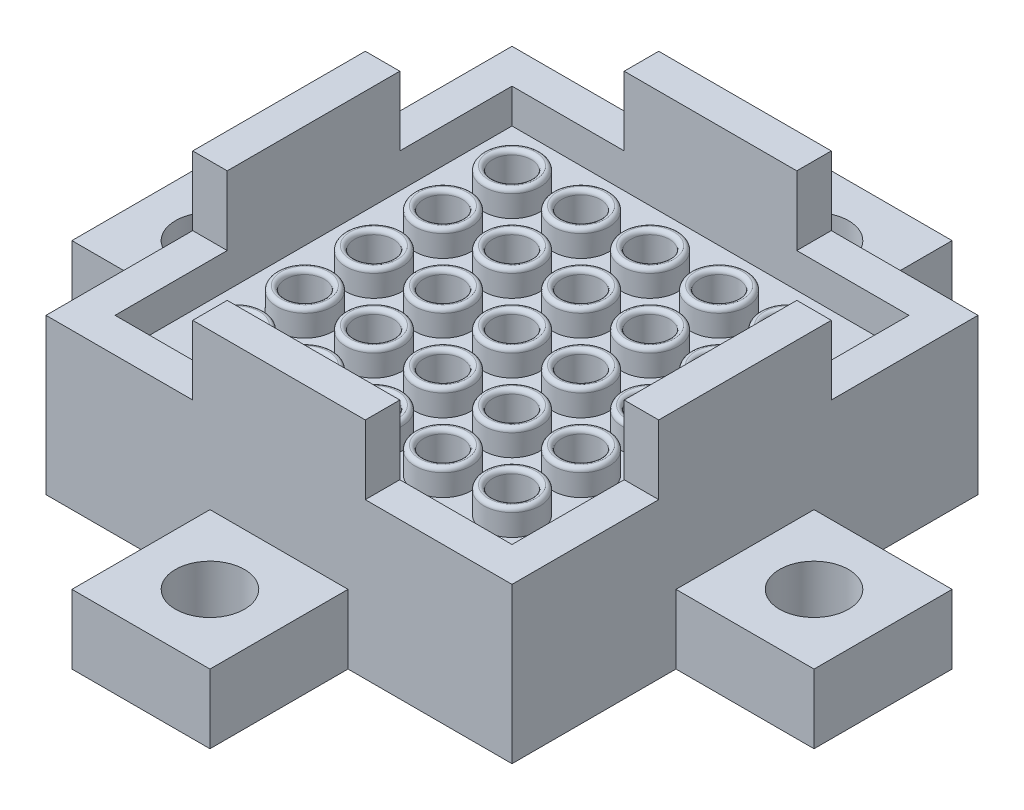
SolidWorks part; units mm, degrees
ref_plane "Front Plane" through (0, 0, 0) normal (0, 0, 1) x (1, 0, 0)
ref_plane "Top Plane" through (0, 0, 0) normal (0, 1, 0) x (1, 0, 0)
ref_plane "Right Plane" through (0, 0, 0) normal (1, 0, 0) x (0, 0, -1)
sketch "Sketch1" plane through (0, 0, 0) normal (0, 1, 0) x (1, 0, 0)
  line L0 (-13.5, 13.5) -> (13.5, 13.5)
  line L1 (-11.5, -11.5) -> (11.5, -11.5)
  line L2 (-11.5, -11.5) -> (-11.5, 11.5)
  line L3 (-11.5, 11.5) -> (11.5, 11.5)
  line L4 (11.5, -11.5) -> (11.5, 11.5)
  line L5 (-11.5, -11.5) -> (11.5, 11.5) construction
  line L6 (-11.5, 11.5) -> (11.5, -11.5) construction
  line L7 (13.5, -13.5) -> (13.5, 13.5)
  line L8 (-13.5, -13.5) -> (13.5, -13.5)
  line L9 (-13.5, -13.5) -> (-13.5, 13.5)
  point P0 (0, 0)
  dimension "D1" = 23
  dimension "D2" = 2
extrude "Boss-Extrude1" add sketch "Sketch1" along normal blind 2
sketch "Sketch2" plane through (0, 0, 0) normal (0, -1, 0) x (1, 0, 0)
  line L1 (-13.5, 13.5) -> (13.5, 13.5)
  line L2 (-13.5, 13.5) -> (-13.5, -13.5)
  line L3 (-13.5, -13.5) -> (13.5, -13.5)
  line L4 (13.5, 13.5) -> (13.5, -13.5)
  line L5 (-13.5, 13.5) -> (13.5, -13.5) construction
  line L6 (-13.5, -13.5) -> (13.5, 13.5) construction
  point P0 (0, 0)
extrude "Boss-Extrude2" add sketch "Sketch2" along normal blind 2
sketch "Sketch3" plane through (0, -2, 0) normal (0, -1, 0) x (1, 0, 0)
  line L0 (-11.5, 11.5) -> (11.5, 11.5)
  line L1 (-13.5, -13.5) -> (13.5, -13.5)
  line L2 (-13.5, -13.5) -> (-13.5, 13.5)
  line L3 (-13.5, 13.5) -> (13.5, 13.5)
  line L4 (13.5, -13.5) -> (13.5, 13.5)
  line L5 (-13.5, -13.5) -> (13.5, 13.5) construction
  line L6 (-13.5, 13.5) -> (13.5, -13.5) construction
  line L7 (11.5, -11.5) -> (11.5, 11.5)
  line L8 (-11.5, -11.5) -> (11.5, -11.5)
  line L9 (-11.5, -11.5) -> (-11.5, 11.5)
  point P0 (0, 0)
  dimension "D1" = 2
extrude "Boss-Extrude3" add sketch "Sketch3" along normal blind 3
sketch "Sketch6" plane through (0, 0, 0) normal (0, 1, 0) x (1, 0, 0)
  line L0 (11.5, -11.5) -> (11.5, 11.5) construction
  line L1 (11.5, 11.5) -> (-11.5, 11.5) construction
  circle A0 centre (8, 8) radius 1.625
  dimension "D2" = 3.25
  dimension "D1" = 3.5
  dimension "D3" = 3.5
extrude "Boss-Extrude5" add sketch "Sketch6" along normal blind 1.5
sketch "Sketch7" plane through (0, 1.5, 0) normal (0, 1, 0) x (1, 0, 0)
  circle A0 centre (8, 8) radius 1.125
  circle A1 centre (8, 8) radius 1.625 construction
  dimension "D1" = 0.5
extrude "Cut-Extrude2" cut sketch "Sketch7" against normal up to next
fillet "Fillet1" radius 0.25 2 edges at (8, 1.5, -6.375) (8, 1.5, -6.875)
pattern_linear "LPattern3" count 5 spacing 4 along (0, 0, 1) count 5 spacing 4 along (-1, 0, 0) of "Boss-Extrude5", "Cut-Extrude2", "Fillet1"
sketch "Sketch11" plane through (0, -2, 0) normal (0, -1, 0) x (1, 0, 0)
  line L0 (11.5, 11.5) -> (-11.5, 11.5) construction
  line L1 (-11.5, 11.5) -> (-11.5, -11.5) construction
  circle A0 centre (-9.9, 9.9) radius 0.75
  dimension "D1" = 1.5
  dimension "D3" = 1.6
  dimension "D2" = 1.6
extrude "Boss-Extrude8" add sketch "Sketch11" along normal up to surface (3 mm away) up to face at (0, -5, 0)
pattern_linear "LPattern2" count 6 spacing 4 along (1, 0, 0) count 6 spacing 4 along (0, 0, -1) of "Boss-Extrude8"
ref_plane "Plane1" through (0, -3.5, 0) normal (0, -1, 0) x (-1, 0, 0)
sketch "Sketch14" plane through (0, -3.5, 0) normal (0, -1, 0) x (-1, 0, 0)
  circle A0 centre (0, 0) radius 2.9698
extrude "Boss-Extrude10" add sketch "Sketch14" against normal blind 0.5
sketch "Sketch8" plane through (0, -5, 0) normal (0, -1, 0) x (1, 0, 0)
  line L1 (-13.5, -13.5) -> (13.5, -13.5)
  line L2 (-13.5, -13.5) -> (-13.5, 13.5)
  line L3 (-13.5, 13.5) -> (13.5, 13.5)
  line L4 (13.5, -13.5) -> (13.5, 13.5)
  line L5 (-13.5, -13.5) -> (13.5, 13.5) construction
  line L6 (-13.5, 13.5) -> (13.5, -13.5) construction
  point P0 (0, 0)
extrude "Boss-Extrude6" add sketch "Sketch8" along normal blind 2
sketch "Sketch9" plane through (0, -7, 0) normal (0, -1, 0) x (1, 0, 0)
  circle A0 centre (0, 0) radius 4.25
  dimension "D1" = 8.5
extrude "Cut-Extrude3" cut sketch "Sketch9" against normal blind 3
sketch "Sketch10" plane through (0, 2, 0) normal (0, 1, 0) x (1, 0, 0)
  line L0 (-13.5, 0) -> (-11.5, 0) construction
  line L1 (-13.5, 13.5) -> (-13.5, -13.5) construction
  line L2 (-11.5, 11.5) -> (-11.5, -11.5) construction
  line L4 (-11.5, 5) -> (-13.5, 5)
  line L5 (-11.5, 5) -> (-11.5, -5)
  line L6 (-11.5, -5) -> (-13.5, -5)
  line L7 (-13.5, 5) -> (-13.5, -5)
  line L8 (-11.5, 5) -> (-13.5, -5) construction
  line L9 (-11.5, -5) -> (-13.5, 5) construction
  point P6 (-12.5, 0)
  dimension "D1" = 10
extrude "Boss-Extrude7" add sketch "Sketch10" along normal blind 4
pattern_circular "CirPattern2" count 4 over 360 about axis through (0, -5.001, 0) along (0, 1, 0) of "Boss-Extrude7"
sketch "Sketch12" plane through (-13.5, 0, 0) normal (-1, 0, 0) x (0, 0, 1)
  line L0 (13.5, -7) -> (-13.5, -7) construction
  line L1 (4, -3) -> (-4, -3)
  line L2 (4, -3) -> (4, -7)
  line L3 (4, -7) -> (-4, -7)
  line L4 (-4, -3) -> (-4, -7)
  line L5 (4, -3) -> (-4, -7) construction
  line L6 (4, -7) -> (-4, -3) construction
  line L7 (0, 0) -> (0, -7) construction
  point P0 (0, -5)
  dimension "D1" = 4
  dimension "D2" = 8
extrude "Boss-Extrude9" add sketch "Sketch12" along normal blind 8
pattern_circular "CirPattern1" count 4 over 360 about axis through (0, -5.001, 0) along (0, 1, 0) of "Boss-Extrude9"
sketch "Sketch16" plane through (0, -3, 0) normal (0, 1, 0) x (1, 0, 0)
  line L0 (-4, -13.5) -> (4, -21.5) construction
  circle A0 centre (0, -17.5) radius 2
  dimension "D1" = 4
extrude "Cut-Extrude4" cut sketch "Sketch16" against normal up to next
pattern_circular "CirPattern3" count 4 over 360 about axis through (0, -5.001, 0) along (0, 1, 0) of "Cut-Extrude4"
sketch "Sketch15" plane through (0, -4, 0) normal (0, -1, 0) x (1, 0, 0)
  circle A0 centre (2.1, 1.9) radius 0.75
  circle A1 centre (-1.9, -2.1) radius 0.75
  circle A2 centre (2.1, -2.1) radius 0.75
  circle A3 centre (-1.9, 1.9) radius 0.75
extrude "Boss-Extrude11" add sketch "Sketch15" along normal up to surface (3 mm away) up to face at (-17.5, -7, 2)
equation "\"D3@Sketch6\"=\"D1@Sketch6\""
equation "\"D3@Sketch11\"=\"D2@Sketch11\""
